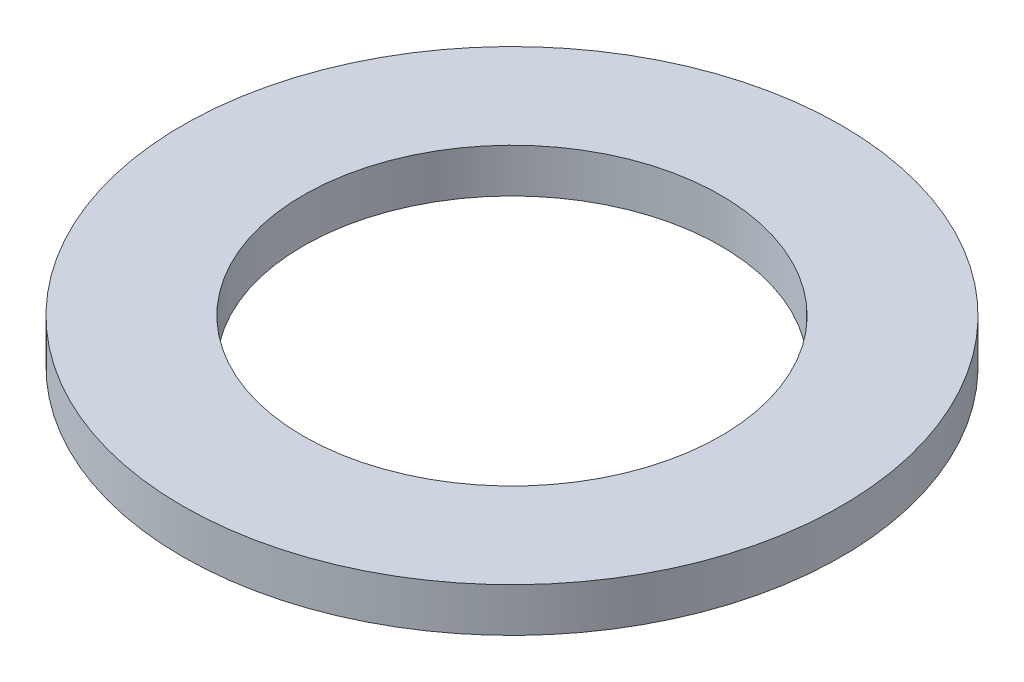
SolidWorks part; units mm, degrees
ref_plane "Front Plane" through (0, 0, 0) normal (0, 0, 1) x (1, 0, 0)
ref_plane "Top Plane" through (0, 0, 0) normal (0, 1, 0) x (1, 0, 0)
ref_plane "Right Plane" through (0, 0, 0) normal (1, 0, 0) x (0, 0, -1)
sketch "Sketch1" plane through (0, 0, 0) normal (0, 1, 0) x (1, 0, 0)
  circle A0 centre (0, 0) radius 75
  dimension "FLANGE_OD" = 150
extrude "Boss-Extrude1" add sketch "Sketch1" along normal blind 10
sketch "Sketch2" plane through (0, 0, 0) normal (0, 1, 0) x (1, 0, 0)
  circle A0 centre (0, 0) radius 47.5
  dimension "BORE_D" = 95
extrude "Cut-Extrude1" cut sketch "Sketch2" along normal through all
sketch "Sketch3" plane through (0, 10, 0) normal (0, 1, 0) x (1, 0, 0)
  circle A0 centre (0, 0) radius 26.6804 construction
  circle A1 centre (-26.6804, 0) radius 4.3047
  dimension "BOLT_D" = 8.6094
  dimension "BOLT_PCD" = 53.3608
extrude "Cut-Extrude2" cut sketch "Sketch3" against normal blind 8.7641 rebuild error yes
pattern_circular "CirPattern1" count 6 over 360 rebuild error yes
